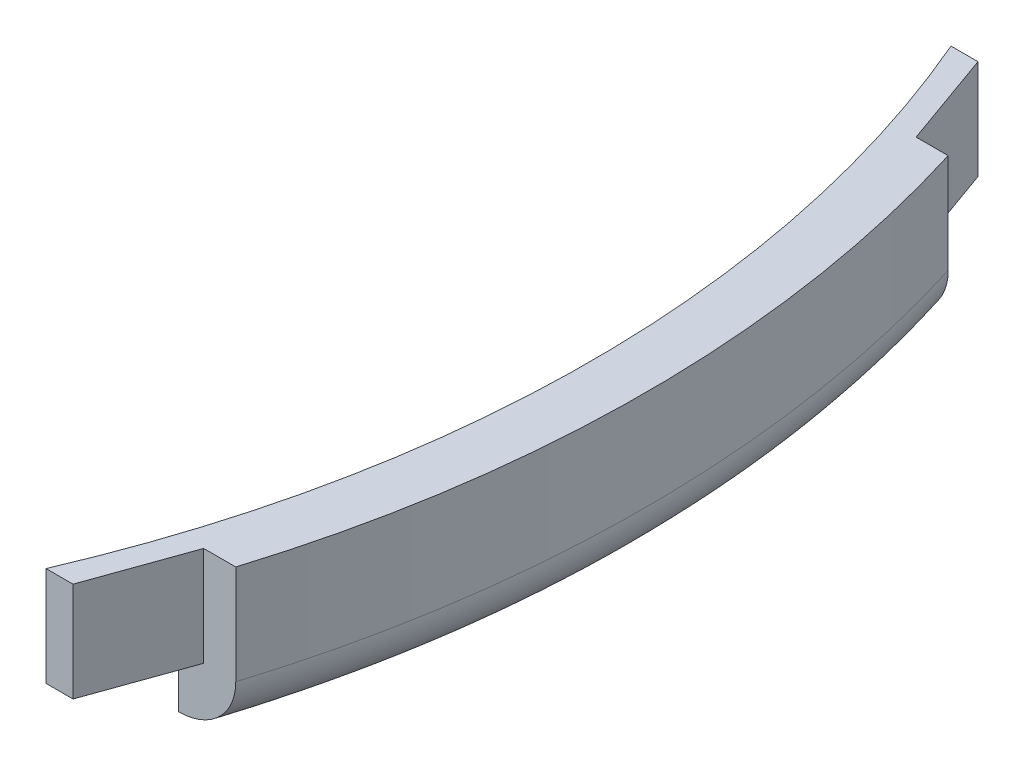
SolidWorks part; units mm, degrees
ref_plane "Front Plane" through (0, 0, 0) normal (0, 0, 1) x (1, 0, 0)
ref_plane "Top Plane" through (0, 0, 0) normal (0, 1, 0) x (1, 0, 0)
ref_plane "Right Plane" through (0, 0, 0) normal (1, 0, 0) x (0, 0, -1)
sketch "Sketch1" plane through (0, 0, 0) normal (0, 1, 0) x (1, 0, 0)
  line L4 (34.8195, 11.1) -> (35.8195, 11.1)
  line L9 (34.8195, -11.1) -> (35.8195, -11.1)
  line L10 (0, 0) -> (50000, 0) construction
  line L11 (32.9064, 14.1) -> (33.7482, 14.1)
  line L12 (33.7482, 14.1) -> (34.8195, 11.1)
  line L13 (33.7482, 14.1) -> (34.7482, 14.1) construction
  line L14 (34.0357, 11.1) -> (34.8195, 11.1) construction
  line L15 (32.9064, -14.1) -> (33.7482, -14.1)
  line L16 (33.7482, -14.1) -> (34.8195, -11.1)
  line L17 (34.8195, -11.1) -> (34.0357, -11.1) construction
  line L18 (33.7482, -14.1) -> (34.7482, -14.1) construction
  arc A0 (32.9064, -14.1) -> (32.9064, 14.1) centre (0, 0) ccw
  arc A1 (35.8195, -11.1) -> (35.8195, 11.1) centre (0, 0) ccw
  arc A2 (35.8195, 11.1) -> (34.7482, 14.1) centre (0, 0) ccw construction
  arc A3 (35.8195, -11.1) -> (34.7482, -14.1) centre (0, 0) cw construction
  dimension "D1" = 71.6
  dimension "D2" = 75
  dimension "D3" = 22.2
  dimension "D4" = 3
  dimension "D5" = 3
  dimension "D6" = 1
extrude "Boss-Extrude1" add sketch "Sketch1" along normal blind 3.6
sketch "Sketch2" plane through (0, 0, 0) normal (0, -1, 0) x (1, 0, 0)
  line L0 (35.8195, 11.1) -> (34.0357, 11.1)
  line L2 (35.8195, -11.1) -> (34.0357, -11.1)
  arc A0 (32.9064, -14.1) -> (32.9064, 14.1) centre (0, 0) ccw construction
  arc A1 (35.8195, -11.1) -> (35.8195, 11.1) centre (0, 0) ccw construction
  arc A2 (34.0357, -11.1) -> (34.0357, 11.1) centre (0, 0) ccw
  arc A3 (35.8195, -11.1) -> (35.8195, 11.1) centre (0, 0) ccw
extrude "Boss-Extrude2" add sketch "Sketch2" along normal blind 1.2
fillet "Fillet1" radius 1.7 1 edges at (37.5, -1.2, 0)
sketch "Sketch3" plane through (34.397, 0, 12.2833) normal (0.9418, 0, 0.3363) x (0.3363, 0, -0.9418)
  line L0 (-1.9291, 3.6) -> (-1.9291, 0) construction
  line L1 (1.1565, 0) -> (1.1565, 2.5689) construction
  line L2 (-1.9291, 0) -> (1.2565, 0) construction
  line L3 (1.1565, 2.5689) -> (-1.9291, 2.5689) construction
  line L4 (1.2565, 3.6) -> (1.2565, 0) construction
  circle A0 centre (-0.3863, 1.8) radius 0.7
  point P4 (-1.9291, 1.8)
  point P12 (-0.3863, 2.5689)
  dimension "D1" = 1.4
  dimension "D2" = 0.1
extrude "Boss-Extrude3" [suppressed] add sketch "Sketch3" along normal blind 1
sketch "Sketch4" plane through (34.397, 0, -12.2833) normal (0.9418, 0, -0.3363) x (-0.3363, 0, -0.9418)
  line L0 (-1.1565, 0) -> (-1.1565, 2.5713) construction
  line L1 (-1.2565, 0) -> (1.9291, 0) construction
  line L2 (-1.1565, 2.5713) -> (1.9291, 2.5713) construction
  line L3 (1.9291, 3.6) -> (1.9291, 0) construction
  line L4 (-1.2565, 3.6) -> (-1.2565, 0) construction
  circle A0 centre (0.3863, 1.8) radius 0.7
  point P12 (0.3863, 2.5713)
  point P13 (1.9291, 1.8)
  dimension "D2" = 1.4
  dimension "D1" = 0.1
extrude "Boss-Extrude4" [suppressed] add sketch "Sketch4" along normal blind 1
sketch "Sketch5" plane through (0, 0, 0) normal (0, -1, 0) x (1, 0, 0)
  line L0 (34.8195, -11.1) -> (34.0357, -11.1) construction
  line L1 (32.9064, -14.1) -> (33.7482, -14.1) construction
  line L2 (33.7482, -14.1) -> (34.8195, -11.1) construction
  line L3 (34.0357, 11.1) -> (34.8195, 11.1) construction
  line L4 (34.8195, 11.1) -> (33.7482, 14.1) construction
  line L5 (33.7482, 14.1) -> (32.9064, 14.1) construction
  line L6 (34.8195, -11.1) -> (34.0357, -11.1)
  line L7 (32.9064, -14.1) -> (33.7482, -14.1)
  line L8 (33.7482, -14.1) -> (34.8195, -11.1)
  line L9 (34.0357, 11.1) -> (34.8195, 11.1)
  line L10 (34.8195, 11.1) -> (33.7482, 14.1)
  line L11 (33.7482, 14.1) -> (32.9064, 14.1)
  arc A0 (32.9064, -14.1) -> (34.0357, -11.1) centre (0, 0) ccw construction
  arc A1 (34.0357, 11.1) -> (32.9064, 14.1) centre (0, 0) ccw construction
  arc A2 (32.9064, -14.1) -> (34.0357, -11.1) centre (0, 0) ccw
  arc A3 (34.0357, 11.1) -> (32.9064, 14.1) centre (0, 0) ccw
extrude "Cut-Extrude1" cut sketch "Sketch5" against normal blind 0.5
